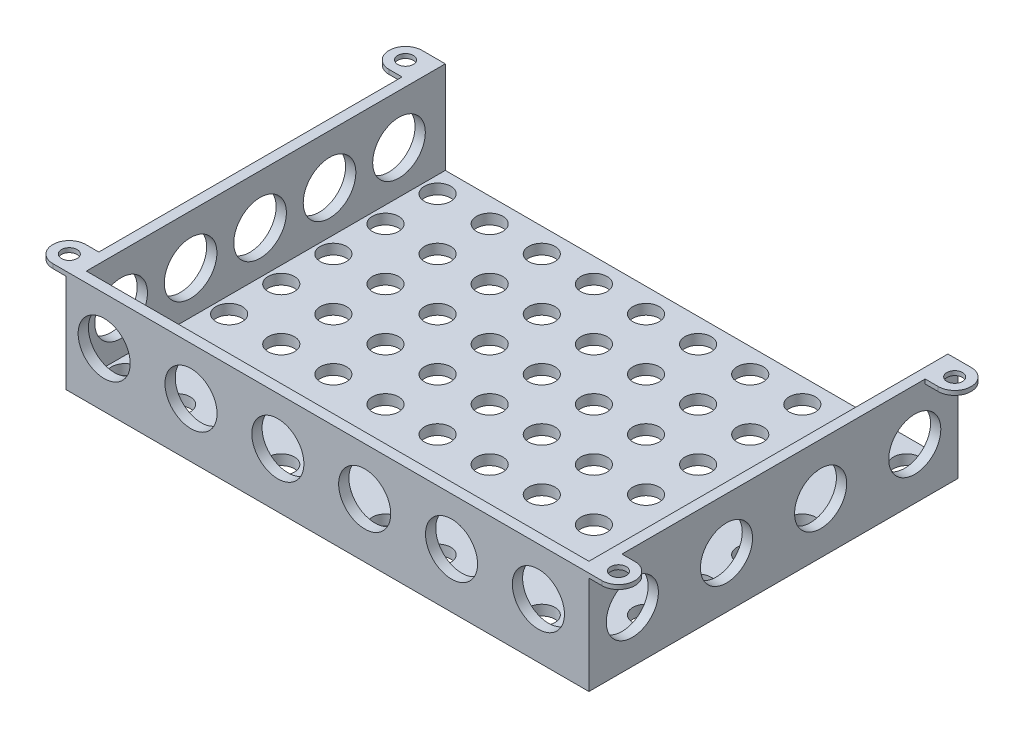
SolidWorks part; units mm, degrees
other "Markup2"
sketch "Sketch32" plane through (-159.4724, 0, 108) normal (-0.262, -0.0774, 0.962) x (0.8638, -0.4632, 0.198)
ref_plane "Front Plane" through (0, 0, 0) normal (0, 0, 1) x (1, 0, 0)
ref_plane "Top Plane" through (0, 0, 0) normal (0, 1, 0) x (1, 0, 0)
ref_plane "Right Plane" through (0, 0, 0) normal (1, 0, 0) x (0, 0, -1)
sketch "Sketch1" plane through (0, 0, 0) normal (0, 1, 0) x (1, 0, 0)
  line L1 (0, 0) -> (-153, 0)
  line L2 (0, 0) -> (0, -108)
  line L3 (0, -108) -> (-153, -108)
  line L4 (-153, 0) -> (-153, -108)
extrude "Boss-Extrude1" add sketch "Sketch1" along normal blind 30 contours L1 L4 L3 L2
shell "Shell1" thickness 3 removed face at (-76.5, 30, 54)
sketch "Sketch7" plane through (0, 30, 0) normal (0, 1, 0) x (1, 0, 0)
  line L0 (-156.81, 0) -> (-153, 0)
  line L1 (-153, 0) -> (-153, -9.652)
  line L2 (-153, 0) -> (-153, -108) construction
  line L3 (-153, -9.652) -> (-156.81, -9.652)
  circle A0 centre (-156.81, -4.826) radius 2.286
  arc A2 (-156.81, 0) -> (-156.81, -9.652) centre (-156.81, -4.826) ccw
  point P2 (-155.0591, -9.52)
  dimension "D1" = 2.54
  dimension "D3" = 4.572
  dimension "D2" = 3.81
extrude "Boss-Extrude7" add sketch "Sketch7" against normal blind 1.27
sketch "Sketch24" plane through (0, 0, 0) normal (0, -1, 0) x (1, 0, 0)
  circle A0 centre (-8.0557, 7.0511) radius 3.8453
extrude "Cut-Extrude8" cut sketch "Sketch24" against normal blind 25.4
pattern_linear "LPattern5" count 10 spacing 15.24 along (-1, 0, 0) of "Cut-Extrude8"
pattern_linear "LPattern6" count 10 spacing 15.24 along (0, 0, 1) of "LPattern5"
sketch "Sketch27" plane through (0, 0, 3) normal (0, 0, 1) x (1, 0, 0)
  line L0 (-3, 3) -> (-3, 30)
  line L1 (-3, 30) -> (-3, 3) construction
  line L2 (-3, 30) -> (-150, 30)
  line L3 (-150, 30) -> (-150, 3)
  line L4 (-150, 3) -> (-3, 3)
extrude "Cut-Extrude10" cut sketch "Sketch27" against normal blind 5.08
sketch "Sketch28" plane through (-153, 0, 0) normal (-1, 0, 0) x (0, 0, 1)
  circle A0 centre (94.8273, 15.5402) radius 7.6982
extrude "Cut-Extrude11" cut sketch "Sketch28" against normal blind 10.16
pattern_linear "LPattern7" count 5 spacing 20.32 along (0, 0, -1) of "Cut-Extrude11"
sketch "Sketch29" plane through (0, 0, 108) normal (0, 0, 1) x (1, 0, 0)
  circle A0 centre (-14.7838, 16.0027) radius 7.62
  dimension "D1" = 15.24
extrude "Cut-Extrude13" cut sketch "Sketch29" against normal blind 7.62 contours A0
pattern_linear "LPattern9" count 6 spacing 25.4 along (-1, 0, 0) of "Cut-Extrude13"
sketch "Sketch30" plane through (0, 0, 0) normal (1, 0, 0) x (0, 0, -1)
  line L0 (0, 30) -> (0, 0) construction
  line L1 (-108, 30) -> (-108, 0) construction
  circle A0 centre (-12.7, 15) radius 7.62
  circle A1 centre (-40.2333, 15) radius 7.62
  circle A2 centre (-67.7667, 15) radius 7.62
  circle A3 centre (-95.3, 15) radius 7.62
  point P12 (0, 0)
  point P13 (0, 15)
  dimension "D2" = 15.24
  dimension "D3" = 12.7
  dimension "D4" = 12.7
  dimension "D1" = 4
extrude "Cut-Extrude14" cut sketch "Sketch30" against normal blind 7.62
ref_plane "Plane1" through (0, 0, 54) normal (0, 0, -1) x (-1, 0, 0)
ref_plane "Plane2" through (-76.5, 0, 0) normal (-1, 0, 0) x (0, 0, 1)
mirror "Mirror1" about plane through (0, 0, 54) normal (0, 0, -1) of "Boss-Extrude7"
mirror "Mirror2" about plane through (-76.5, 0, 0) normal (-1, 0, 0) of "Mirror1"
